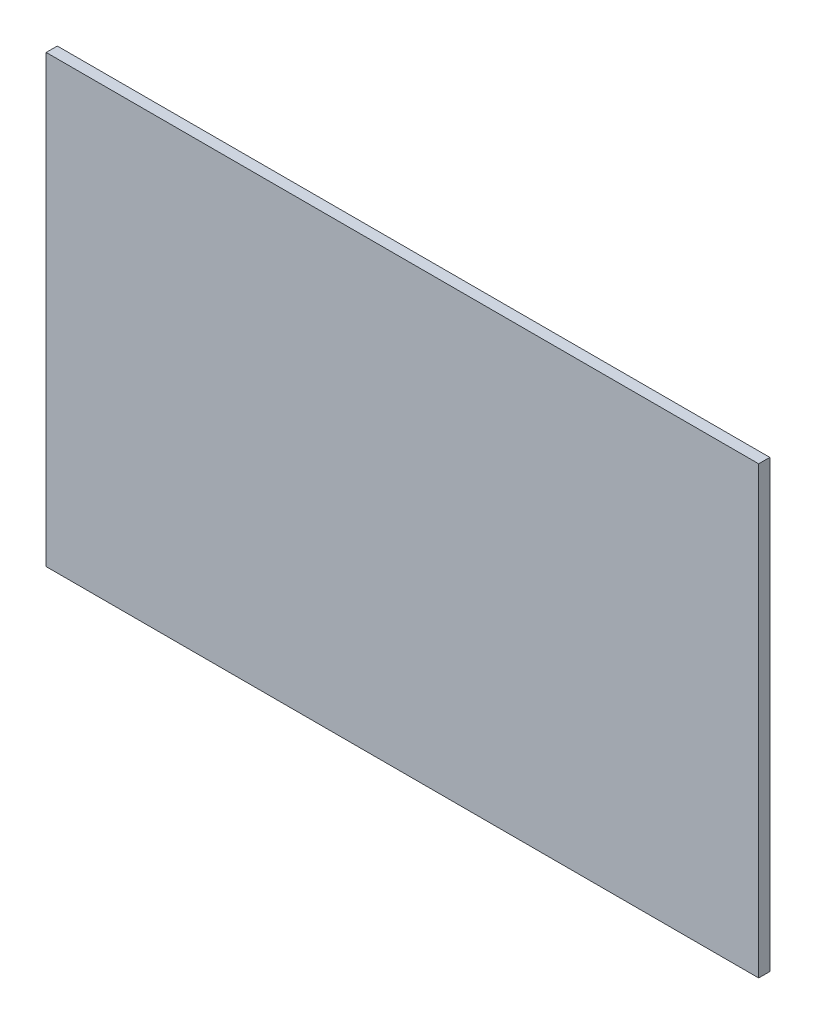
SolidWorks part; units mm, degrees
material "Oak"
ref_plane "Front Plane" through (0, 0, 0) normal (0, 0, 1) x (1, 0, 0)
ref_plane "Top Plane" through (0, 0, 0) normal (0, 1, 0) x (1, 0, 0)
ref_plane "Right Plane" through (0, 0, 0) normal (1, 0, 0) x (0, 0, -1)
sketch "Sketch1" plane through (0, 0, 0) normal (0, 0, 1) x (1, 0, 0)
  line L1 (-160, 100) -> (160, 100)
  line L2 (-160, 100) -> (-160, -100)
  line L3 (-160, -100) -> (160, -100)
  line L4 (160, 100) -> (160, -100)
  line L5 (-160, 100) -> (160, -100) construction
  line L6 (-160, -100) -> (160, 100) construction
  point P0 (0, 0)
  dimension "D1" = 320
  dimension "D2" = 200
base flange "Base-Flange1" sketch "Sketch1" thickness 5 reverse thickness direction no parameters "D1"=0.7366
sketch "Bend-Lines1" [suppressed] plane through (0, 0, 0) normal (0, 1, 0) x (1, 0, 0)
sketch "Bounding-Box1" [suppressed] plane through (0, 0, 0) normal (0, 1, 0) x (1, 0, 0)
sheet metal parameters "Sheet-Metal1" thickness 5 parameters "D1"=0.7366
flat pattern "Flat-Pattern1" [suppressed]
sketch "Bend-Lines2" plane through (0, 0, 0) normal (0, 1, 0) x (1, 0, 0)
sketch3d "Bounding-Box2" [suppressed]
  line L0 (-160, -100, 0) -> (160, -100, 0) construction
  line L1 (-160, 100, 0) -> (160, 100, 0) construction
  line L2 (-160, -100, 0) -> (-160, 100, 0) construction
  line L3 (160, -100, 0) -> (160, 100, 0) construction
